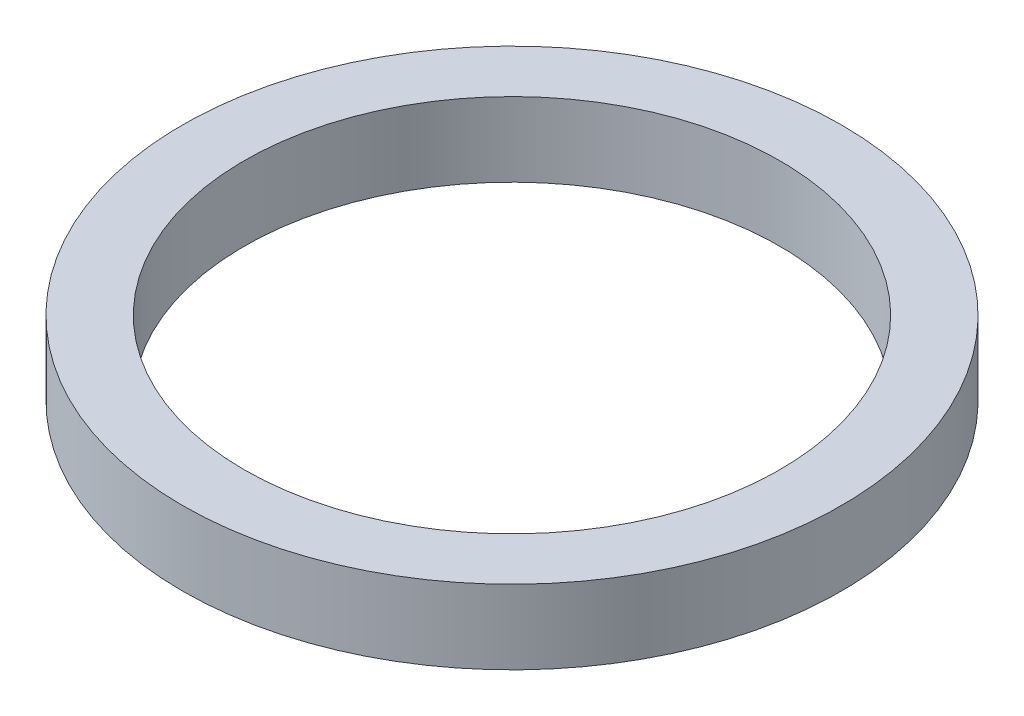
SolidWorks part; units mm, degrees
ref_plane "Front Plane" through (0, 0, 0) normal (0, 0, 1) x (1, 0, 0)
ref_plane "Top Plane" through (0, 0, 0) normal (0, 1, 0) x (1, 0, 0)
ref_plane "Right Plane" through (0, 0, 0) normal (1, 0, 0) x (0, 0, -1)
sketch "Sketch1" plane through (0, 0, 0) normal (0, 1, 0) x (1, 0, 0)
  circle A0 centre (0, 0) radius 40
  dimension "FLANGE_OD" = 80
extrude "Boss-Extrude1" add sketch "Sketch1" along normal blind 9
sketch "Sketch2" plane through (0, 0, 0) normal (0, 1, 0) x (1, 0, 0)
  circle A0 centre (0, 0) radius 32.5
  dimension "BORE_D" = 65
extrude "Cut-Extrude1" cut sketch "Sketch2" along normal through all
sketch "Sketch3" plane through (0, 9, 0) normal (0, 1, 0) x (1, 0, 0)
  circle A0 centre (0, 0) radius 17.5952 construction
  circle A1 centre (-17.5952, 0) radius 1.5
  dimension "BOLT_D" = 3
  dimension "BOLT_PCD" = 35.1904
extrude "Cut-Extrude2" cut sketch "Sketch3" against normal blind 7.5061 rebuild error yes
pattern_circular "CirPattern1" count 4 over 360 rebuild error yes
